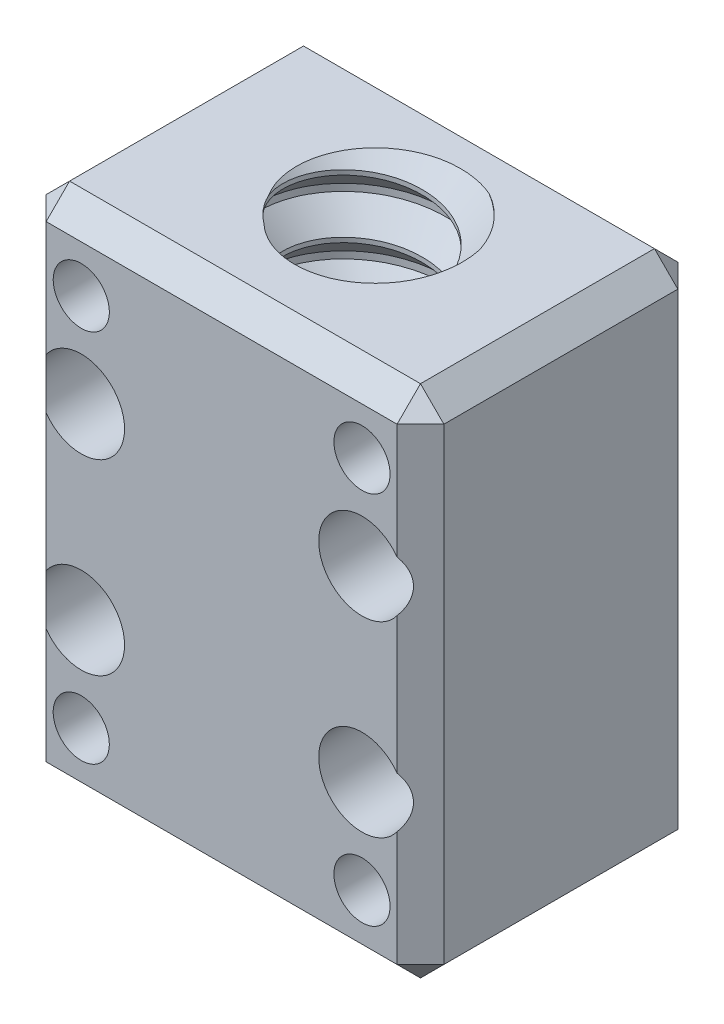
SolidWorks part; units mm, degrees
ref_plane "前视基准面" through (0, 0, 0) normal (0, 0, 1) x (1, 0, 0)
ref_plane "上视基准面" through (0, 0, 0) normal (0, 1, 0) x (1, 0, 0)
ref_plane "右视基准面" through (0, 0, 0) normal (1, 0, 0) x (0, 0, -1)
sketch "草图1" plane through (0, 0, 0) normal (0, 0, 1) x (1, 0, 0)
  line L1 (-8.5, -11) -> (8.5, -11)
  line L2 (-8.5, -11) -> (-8.5, 11)
  line L3 (-8.5, 11) -> (8.5, 11)
  line L4 (8.5, -11) -> (8.5, 11)
  line L5 (-8.5, -11) -> (8.5, 11) construction
  line L6 (-8.5, 11) -> (8.5, -11) construction
  point P0 (0, 0)
  dimension "D1" = 17
  dimension "D2" = 22
extrude "凸台-拉伸1" add sketch "草图1" along normal blind 12
sketch "草图2" plane through (0, -11, 0) normal (0, -1, 0) x (1, 0, 0)
  line L0 (-8.5, 6) -> (8.5, 6) construction
  line L1 (-8.5, 12) -> (-8.5, 0) construction
  line L2 (8.5, 12) -> (8.5, 0) construction
  line L3 (0, 0) -> (0, 12) construction
  line L4 (-8.5, 12) -> (8.5, 12) construction
  circle A0 centre (0, 6) radius 4
  dimension "D1" = 8
extrude "切除-拉伸1" cut sketch "草图2" against normal up to next
sketch "草图3" plane through (0, -11, 0) normal (0, -1, 0) x (1, 0, 0)
  circle A0 centre (0, 6) radius 4 construction
  circle A1 centre (0, 6) radius 4
curve "螺旋线/涡状线1" pitch 2.5 height 22.5 radius 4 centre (0, -11, 6) axis (0, 1, 0) start towards (0, 0, -1)
sketch "草图6" plane through (0, 0, 0) normal (1, 0, 0) x (0, 0, -1)
  line L0 (-2, -8.8) -> (-2, -11)
  line L1 (-2, -11) -> (-3, -10)
  line L2 (-3, -10) -> (-3, -9.8)
  line L3 (-3, -9.8) -> (-2, -8.8)
  point P2 (-3, -9.9)
  point P5 (-2, -9.9)
  dimension "D1" = 2.2
  dimension "D2" = 1
  dimension "D3" = 45
sweep "扫描1" add profiles "草图6" path "螺旋线/涡状线1"
sketch "草图7" plane through (0, 11, 0) normal (0, 1, 0) x (1, 0, 0)
  circle A0 centre (0, -6) radius 15.4839
extrude "切除-拉伸3" cut sketch "草图7" along normal blind 30
sketch "草图8" plane through (0, 0, 12) normal (0, 0, 1) x (1, 0, 0)
  line L0 (-14.8745, 4) -> (15.9779, 4) construction
  line L1 (0, 6.1723) -> (0, -6.7506) construction
  line L2 (-2.9516, 0) -> (3.5387, 0) construction
  line L3 (0, -6.1723) -> (0, 6.7506) construction
  line L4 (-14.8745, -4) -> (15.9779, -4) construction
  circle A0 centre (6, 4) radius 1.1
  circle A1 centre (-6, 4) radius 1.1
  circle A2 centre (-6, -4) radius 1.1
  circle A3 centre (6, -4) radius 1.1
  dimension "D1" = 2.2
  dimension "D2" = 12
  dimension "D3" = 8
extrude "切除-拉伸4" cut sketch "草图8" against normal through all
sketch "草图9" plane through (0, 0, 12) normal (0, 0, 1) x (1, 0, 0)
  circle A0 centre (-6, 4) radius 1.85
  circle A1 centre (6, 4) radius 1.85
  circle A2 centre (6, -4) radius 1.85
  circle A3 centre (-6, -4) radius 1.85
  dimension "D1" = 3.7
  dimension "D2" = 3.7
  dimension "D3" = 3.7
  dimension "D4" = 3.7
extrude "切除-拉伸5" cut sketch "草图9" against normal blind 7
sketch "草图10" plane through (0, 0, 12) normal (0, 0, 1) x (1, 0, 0)
  line L0 (-9.8772, 0) -> (10.0907, 0) construction
  line L1 (0, 11.8176) -> (0, -11.5673) construction
  circle A0 centre (6, 8) radius 1.2
  circle A1 centre (-6, 8) radius 1.2
  circle A2 centre (6, -8) radius 1.2
  circle A3 centre (-6, -8) radius 1.2
  dimension "D1" = 2.4
  dimension "D2" = 8
  dimension "D3" = 6
extrude "切除-拉伸6" cut sketch "草图10" against normal blind 7
fillet "圆角1" radius 1 12 edges at (8.5, -11, 6) (8.5, 11, 6) (0, 11, 0) (0, -11, 0) (8.5, 0, 0) (0, -11, 12) (0, 11, 12) (8.5, 0, 12) (-8.5, 11, 6) (-8.5, 0, 12) (-8.5, -11, 6) (-8.5, 0, 0) profile chamfer
